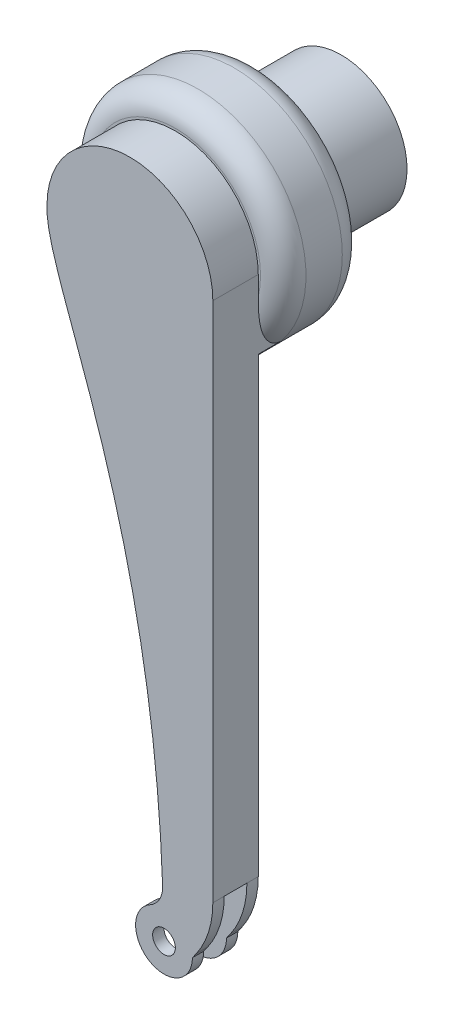
SolidWorks part; units mm, degrees
ref_plane "Front Plane" through (0, 0, 0) normal (0, 0, 1) x (1, 0, 0)
ref_plane "Top Plane" through (0, 0, 0) normal (0, 1, 0) x (1, 0, 0)
ref_plane "Right Plane" through (0, 0, 0) normal (1, 0, 0) x (0, 0, -1)
sketch "Sketch1" plane through (0, 0, 0) normal (0, 0, 1) x (1, 0, 0)
  circle A0 centre (0, 0) radius 47.5
extrude "Boss-Extrude1" add sketch "Sketch1" along normal blind 36
sketch "Sketch2" plane through (0, 0, 0) normal (0, 0, -1) x (-1, 0, 0)
  line L0 (0, 0) -> (0, -36.5) construction
  line L1 (0, -255) -> (-15, -255) construction
  line L2 (-29.1731, -252.631) -> (-27.5, -255)
  line L3 (0, -244.9103) -> (0, -255) construction
  line L4 (-36.5, 0) -> (-36.5, -229.5557)
  arc A0 (36.5, -0.0228) -> (-36.5, 0) centre (0, 0) ccw
  arc A1 (-27.5, -255) -> (-8.8693, -244.1067) centre (-15, -255) ccw
  arc A3 (-29.1731, -252.631) -> (-36.5, -229.5557) centre (3.5, -229.5557) cw
  arc A4 (-14.3935, -234.1239) -> (-8.8693, -244.1067) centre (-3.5402, -234.6378) ccw
  spline S0 degree 3 poles (36.5, -0.0228) (37.9578, -27.6639) (-9.3418, -94.6674) (-14.3935, -234.1239) knots 0 0 0 0 0.878387 0.878387 0.878387 0.878387
  dimension "D1" = 255
  dimension "D3" = 40
  dimension "D4" = 73
  dimension "D2" = 15
extrude "Boss-Extrude2" add sketch "Sketch2" along normal blind 20
sketch "Sketch3" plane through (0, 0, 36) normal (0, 0, 1) x (1, 0, 0)
  circle A0 centre (0, 0) radius 29
extrude "Boss-Extrude3" add sketch "Sketch3" along normal blind 37
fillet "Fillet1" radius 10 1 edges at (-7.1112, 46.9647, 0)
fillet "Fillet2" radius 10 1 edges at (47.5, 0, 36)
sketch "Sketch5" plane through (0, 0, -20) normal (0, 0, -1) x (-1, 0, 0)
  circle A0 centre (-15, -255) radius 5
  arc A1 (-27.5, -255) -> (-8.8693, -244.1067) centre (-15, -255) ccw construction
extrude "Cut-Extrude1" cut sketch "Sketch5" against normal blind 37
mirror "Mirror7" about plane through (0, 0, 73) normal (0, 0, 1) of bodies 104 107
delete or keep bodies "Body-Delete/Keep 1" type delete bodies bodies 104
sketch "Sketch6" plane through (0, 0, 0) normal (1, 0, 0) x (0, 0, -1)
  line L0 (-166, -229.5557) -> (-146, -229.5557) construction
  line L1 (-161, -229.5557) -> (-151, -229.5557)
  line L2 (-161, -229.5557) -> (-161, -270.2721)
  line L3 (-161, -270.2721) -> (-151, -270.2721)
  line L4 (-151, -229.5557) -> (-151, -270.2721)
  line L5 (-166, -229.5557) -> (-166, -252.631) construction
  dimension "D1" = 10
  dimension "D2" = 5
extrude "Cut-Extrude2" cut sketch "Sketch6" along normal blind 45
